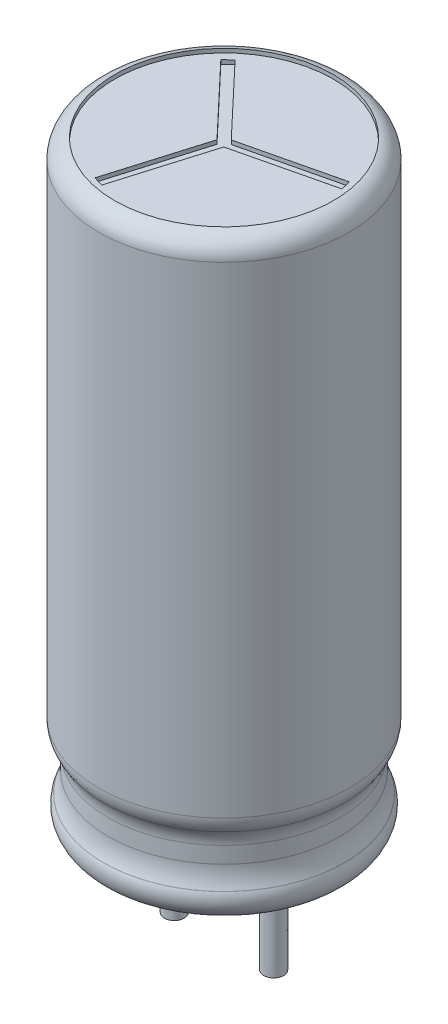
SolidWorks part; units mm, degrees
ref_plane "Front Plane" through (0, 0, 0) normal (0, 0, 1) x (1, 0, 0)
ref_plane "Top Plane" through (0, 0, 0) normal (0, 1, 0) x (1, 0, 0)
ref_plane "Right Plane" through (0, 0, 0) normal (1, 0, 0) x (0, 0, -1)
sketch "Sketch1" plane through (0, 0, 0) normal (0, 0, 1) x (1, 0, 0)
  line L0 (3.15, 15) -> (0, 15)
  line L1 (0, 15) -> (0, 0)
  line L2 (0, 0) -> (3.0302, 0)
  line L3 (2.9104, 1.2326) -> (2.9104, 1.6424)
  line L4 (3.15, 2.4076) -> (3.15, 15)
  line L5 (0, 15) -> (0, 0) construction
  arc A0 (3.0302, 0) -> (3.0302, 0.7254) centre (2.3052, 0.3627) ccw
  arc A1 (3.0302, 0.7254) -> (2.9104, 1.2326) centre (4.0441, 1.2326) cw
  arc A2 (2.9104, 1.6424) -> (3.0302, 2.025) centre (3.5813, 1.6424) cw
  arc A3 (3.0302, 2.025) -> (3.15, 2.4076) centre (2.4792, 2.4076) ccw
  point P14 (3.15, 0.6187)
  point P15 (3.0302, 0.0609)
  point P16 (3.0856, 0.6121)
  point P17 (3.0856, 0.0684)
  point P18 (3.0302, 0.7254)
  point P19 (3.0302, 0)
  dimension "D1" = 15
  dimension "D2" = 3.15
revolve "Revolve1" add sketch "Sketch1" angle 360 about L5 reverse direction yes
sketch "Sketch2" plane through (0, 15, 0) normal (0, 1, 0) x (-1, 0, 0)
  circle A0 centre (0, 0) radius 2.75
extrude "Cut-Extrude1" cut sketch "Sketch2" against normal blind 0.1
sketch "Sketch3" plane through (0, 14.9, 0) normal (0, 1, 0) x (-1, 0, 0)
  line L0 (1.6535, -1.9323) -> (1.838, -1.7577)
  line L1 (1.838, -1.7577) -> (0.1426, 0.034)
  line L2 (0.1426, 0.034) -> (0.8467, 2.3981)
  line L3 (0.8467, 2.3981) -> (0.6032, 2.4706)
  line L4 (0.6032, 2.4706) -> (-0.1008, 0.1065)
  line L5 (-0.1008, 0.1065) -> (-2.5002, -0.4658)
  line L6 (-2.5002, -0.4658) -> (-2.4412, -0.7129)
  line L7 (-2.4412, -0.7129) -> (-0.0419, -0.1405)
  line L8 (-0.0419, -0.1405) -> (1.6535, -1.9323)
extrude "Cut-Extrude2" cut sketch "Sketch3" against normal blind 0.1
ref_plane "Plane1" through (0, 0, 0) normal (0, 0, -1) x (-1, 0, 0)
fillet "Fillet1" radius 0.5 2 edges at (0, 15, -3.15) (0, 0, -3.0302) tangent propagation no
sketch "Sketch4" plane through (0, 0, 0) normal (0, 0, -1) x (-1, 0, 0)
  line L0 (-1.5, -2.5) -> (-1.25, -2.5)
  line L1 (-1.25, -2.5) -> (-1.25, 0)
  line L2 (-1.25, 0) -> (-1.5, 0)
  line L3 (-1.5, 0) -> (-1.5, -2.5)
  line L4 (-1.25, -2.5) -> (-1.25, 0) construction
  dimension "D1" = 1.25
  dimension "D2" = 0.25
revolve "Revolve2" add sketch "Sketch4" angle 360 about L4 reverse direction yes
mirror "Simetría2" about plane through (0, 0, 0) normal (1, 0, 0) of "Revolve2"
